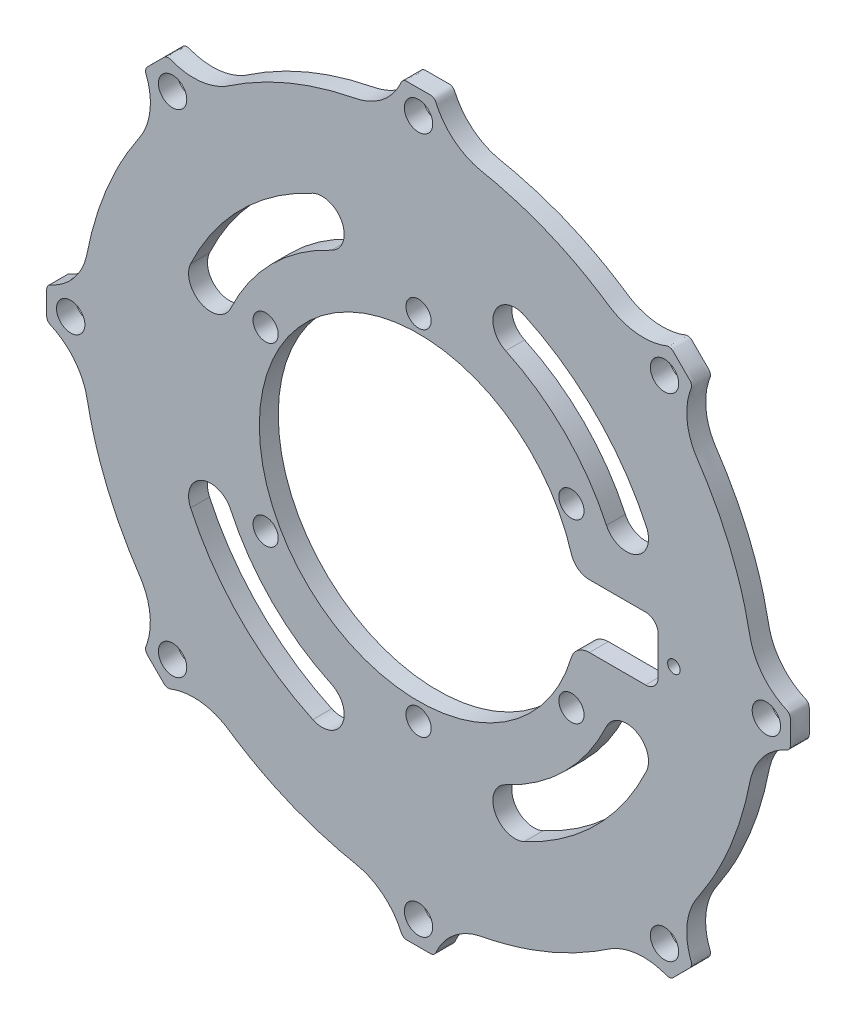
SolidWorks part; units mm, degrees
material "7075-T6, Plate (SS)"
ref_plane "Front Plane" through (0, 0, 0) normal (0, 0, 1) x (1, 0, 0)
ref_plane "Top Plane" through (0, 0, 0) normal (0, 1, 0) x (1, 0, 0)
ref_plane "Right Plane" through (0, 0, 0) normal (1, 0, 0) x (0, 0, -1)
sketch "Sketch1" plane through (0, 0, 0) normal (0, 0, 1) x (1, 0, 0)
  line L0 (0, 0) -> (15.2936, 32.9713) construction
  line L1 (-3.9972, 40.3023) -> (0, 28) construction
  line L3 (38, -3) -> (38, 3) construction
  line L4 (38, -3) -> (38, 3)
  line L5 (36, 5) -> (27.0936, 5)
  line L6 (36, -5) -> (27.0936, -5)
  line L7 (0, 0) -> (0, 48) construction
  line L8 (-2.8886, 58.0903) -> (-2.7624, 58.3675)
  line L9 (-1.8466, 58.9658) -> (1.8466, 58.9658) construction
  line L10 (2.7624, 58.3675) -> (2.7687, 58.3533)
  line L11 (-5, 53.2658) -> (5, 53.2658) construction
  line L12 (40.3894, 43.0009) -> (43.0009, 40.3894) construction
  line L13 (39.3043, 43.2198) -> (39.3187, 43.2254) construction
  line L14 (43.2254, 39.3187) -> (43.2198, 39.3043) construction
  line L15 (58.9658, 1.8466) -> (58.9658, -1.8466) construction
  line L16 (58.3533, 2.7687) -> (58.3675, 2.7624) construction
  line L17 (58.3675, -2.7624) -> (58.3533, -2.7687) construction
  line L18 (43.0009, -40.3894) -> (40.3894, -43.0009) construction
  line L19 (43.2198, -39.3043) -> (43.2254, -39.3187) construction
  line L20 (39.3187, -43.2254) -> (39.3043, -43.2198) construction
  line L21 (1.8466, -58.9658) -> (-1.8466, -58.9658) construction
  line L22 (2.7687, -58.3533) -> (2.7624, -58.3675) construction
  line L23 (-2.7624, -58.3675) -> (-2.7687, -58.3533) construction
  line L24 (-40.3894, -43.0009) -> (-43.0009, -40.3894) construction
  line L25 (-39.3043, -43.2198) -> (-39.3187, -43.2254) construction
  line L26 (-43.2254, -39.3187) -> (-43.2198, -39.3043) construction
  line L27 (-58.9658, -1.8466) -> (-58.9658, 1.8466) construction
  line L28 (-58.3533, -2.7687) -> (-58.3675, -2.7624) construction
  line L29 (-58.3675, 2.7624) -> (-58.3533, 2.7687) construction
  line L30 (-43.0009, 40.3894) -> (-40.3894, 43.0009) construction
  line L31 (-43.2198, 39.3043) -> (-43.2254, 39.3187) construction
  line L32 (-39.3187, 43.2254) -> (-39.3043, 43.2198) construction
  line L33 (0, 0) -> (25.7002, 25.7002) construction
  arc A0 (-10.0483, 52.5479) -> (-30.0517, 44.2622) centre (0, 0) ccw construction
  circle A1 centre (0, 0) radius 28 construction
  arc A3 (24.2164, 7.1504) -> (24.2164, -7.1504) centre (0, 0) ccw
  arc A4 (38, 3) -> (34, 3) centre (36, 3) ccw construction
  arc A5 (34, -3) -> (38, -3) centre (36, -3) ccw construction
  arc A6 (36, -5) -> (38, -3) centre (36, -3) ccw
  arc A7 (38, 3) -> (36, 5) centre (36, 3) ccw
  arc A8 (27.0936, -5) -> (24.2164, -7.1504) centre (27.0936, -8) ccw
  arc A9 (27.0936, 5) -> (24.2164, 7.1504) centre (27.0936, 8) cw
  circle A10 centre (0, 0) radius 36.3456 construction
  arc A13 (15.2936, 32.9713) -> (32.9713, 15.2936) centre (0, 0) cw construction
  circle A72 centre (0, 0) radius 40.5 construction
  circle A81 centre (40.4993, -0.2374) radius 1
  arc A104 (-2.8886, 58.0903) -> (-10.0483, 52.5479) centre (-11.9265, 62.3699) cw construction
  arc A105 (2.7687, 58.3533) -> (10.0483, 52.5479) centre (11.9265, 62.3699) ccw construction
  arc A106 (39.3043, 43.2198) -> (30.0517, 44.2622) centre (35.6689, 52.5355) cw construction
  arc A107 (43.2198, 39.3043) -> (44.2622, 30.0517) centre (52.5355, 35.6689) ccw construction
  arc A108 (58.3533, 2.7687) -> (52.5479, 10.0483) centre (62.3699, 11.9265) cw construction
  arc A109 (58.3533, -2.7687) -> (52.5479, -10.0483) centre (62.3699, -11.9265) ccw construction
  arc A110 (43.2198, -39.3043) -> (44.2622, -30.0517) centre (52.5355, -35.6689) cw construction
  arc A111 (39.3043, -43.2198) -> (30.0517, -44.2622) centre (35.6689, -52.5355) ccw construction
  arc A112 (2.7687, -58.3533) -> (10.0483, -52.5479) centre (11.9265, -62.3699) cw construction
  arc A113 (-2.7687, -58.3533) -> (-10.0483, -52.5479) centre (-11.9265, -62.3699) ccw construction
  arc A114 (-39.3043, -43.2198) -> (-30.0517, -44.2622) centre (-35.6689, -52.5355) cw construction
  arc A115 (-43.2198, -39.3043) -> (-44.2622, -30.0517) centre (-52.5355, -35.6689) ccw construction
  arc A116 (-58.3533, -2.7687) -> (-52.5479, -10.0483) centre (-62.3699, -11.9265) cw construction
  arc A117 (-58.3533, 2.7687) -> (-52.5479, 10.0483) centre (-62.3699, 11.9265) ccw construction
  arc A118 (-43.2198, 39.3043) -> (-44.2622, 30.0517) centre (-52.5355, 35.6689) cw construction
  arc A119 (-39.3043, 43.2198) -> (-30.0517, 44.2622) centre (-35.6689, 52.5355) ccw construction
  arc A120 (30.0517, 44.2622) -> (10.0483, 52.5479) centre (0, 0) ccw construction
  arc A121 (52.5479, 10.0483) -> (44.2622, 30.0517) centre (0, 0) ccw construction
  arc A122 (10.0483, -52.5479) -> (30.0517, -44.2622) centre (0, 0) ccw construction
  arc A123 (44.2622, -30.0517) -> (52.5479, -10.0483) centre (0, 0) ccw construction
  arc A124 (-30.0517, -44.2622) -> (-10.0483, -52.5479) centre (0, 0) ccw construction
  arc A125 (-52.5479, -10.0483) -> (-44.2622, -30.0517) centre (0, 0) ccw construction
  arc A126 (-44.2622, 30.0517) -> (-52.5479, 10.0483) centre (0, 0) ccw construction
  arc A127 (1.8466, 58.9658) -> (2.7624, 58.3675) centre (1.8466, 57.9658) cw construction
  arc A128 (-2.7624, 58.3675) -> (-1.8466, 58.9658) centre (-1.8466, 57.9658) cw construction
  arc A129 (-43.0009, 40.3894) -> (-43.2254, 39.3187) centre (-42.2938, 39.6823) ccw construction
  arc A130 (-40.3894, 43.0009) -> (-39.3187, 43.2254) centre (-39.6823, 42.2938) cw construction
  arc A131 (-58.9658, 1.8466) -> (-58.3675, 2.7624) centre (-57.9658, 1.8466) cw construction
  arc A132 (-58.9658, -1.8466) -> (-58.3675, -2.7624) centre (-57.9658, -1.8466) ccw construction
  arc A133 (-43.0009, -40.3894) -> (-43.2254, -39.3187) centre (-42.2938, -39.6823) cw construction
  arc A134 (-40.3894, -43.0009) -> (-39.3187, -43.2254) centre (-39.6823, -42.2938) ccw construction
  arc A135 (-1.8466, -58.9658) -> (-2.7624, -58.3675) centre (-1.8466, -57.9658) cw construction
  arc A136 (1.8466, -58.9658) -> (2.7624, -58.3675) centre (1.8466, -57.9658) ccw construction
  arc A137 (43.0009, -40.3894) -> (43.2254, -39.3187) centre (42.2938, -39.6823) ccw construction
  arc A138 (40.3894, -43.0009) -> (39.3187, -43.2254) centre (39.6823, -42.2938) cw construction
  arc A139 (58.9658, -1.8466) -> (58.3675, -2.7624) centre (57.9658, -1.8466) cw construction
  arc A140 (58.9658, 1.8466) -> (58.3675, 2.7624) centre (57.9658, 1.8466) ccw construction
  arc A141 (43.0009, 40.3894) -> (43.2254, 39.3187) centre (42.2938, 39.6823) cw construction
  arc A142 (40.3894, 43.0009) -> (39.3187, 43.2254) centre (39.6823, 42.2938) ccw construction
  arc A143 (36.1463, 16.7664) -> (16.7664, 36.1463) centre (0, 0) ccw
  arc A144 (29.7962, 13.8209) -> (13.8209, 29.7962) centre (0, 0) ccw
  arc A145 (29.7962, 13.8209) -> (36.1463, 16.7664) centre (32.9713, 15.2936) ccw
  arc A146 (16.7664, 36.1463) -> (13.8209, 29.7962) centre (15.2936, 32.9713) ccw
  arc A147 (32.9713, -15.2936) -> (15.2936, -32.9713) centre (0, 0) cw construction
  arc A148 (16.7664, -36.1463) -> (36.1463, -16.7664) centre (0, 0) ccw
  arc A149 (13.8209, -29.7962) -> (29.7962, -13.8209) centre (0, 0) ccw
  arc A150 (13.8209, -29.7962) -> (16.7664, -36.1463) centre (15.2936, -32.9713) ccw
  arc A151 (36.1463, -16.7664) -> (29.7962, -13.8209) centre (32.9713, -15.2936) ccw
  arc A152 (-15.2936, -32.9713) -> (-32.9713, -15.2936) centre (0, 0) cw construction
  arc A153 (-36.1463, -16.7664) -> (-16.7664, -36.1463) centre (0, 0) ccw
  arc A154 (-29.7962, -13.8209) -> (-13.8209, -29.7962) centre (0, 0) ccw
  arc A155 (-29.7962, -13.8209) -> (-36.1463, -16.7664) centre (-32.9713, -15.2936) ccw
  arc A156 (-16.7664, -36.1463) -> (-13.8209, -29.7962) centre (-15.2936, -32.9713) ccw
  arc A157 (-32.9713, 15.2936) -> (-15.2936, 32.9713) centre (0, 0) cw construction
  arc A158 (-16.7664, 36.1463) -> (-36.1463, 16.7664) centre (0, 0) ccw
  arc A159 (-13.8209, 29.7962) -> (-29.7962, 13.8209) centre (0, 0) ccw
  arc A160 (-13.8209, 29.7962) -> (-16.7664, 36.1463) centre (-15.2936, 32.9713) ccw
  arc A161 (-36.1463, 16.7664) -> (-29.7962, 13.8209) centre (-32.9713, 15.2936) ccw
  spline S0 degree 3 poles (-2.8886, 58.0903) (-3.9043, 55.9453) (-5.5918, 54.2764) (-7.7481, 53.2847) (-8.2352, 53.0607) (-9.2456, 52.691) (-10.8423, 52.3981) (-11.8892, 52.165) (-12.4107, 52.0406) (-17.936, 50.7229) (-23.1839, 48.5492) (-28.0226, 45.574) (-28.4793, 45.2931) (-29.3844, 44.7177) (-30.7205, 43.7957) (-31.6964, 43.3428) (-32.1993, 43.1567) (-34.5203, 42.2981) (-36.9949, 42.3196) (-39.3007, 43.2183) (-39.3011, 43.2185) (-39.3019, 43.2188) (-39.3031, 43.2193) (-39.3039, 43.2196) (-39.3043, 43.2198) (-39.3047, 43.2199) (-39.3055, 43.2202) (-39.3067, 43.2207) (-39.3075, 43.221) (-39.3079, 43.2212) (-39.3103, 43.2221) (-39.3127, 43.223) (-39.3151, 43.224) (-39.3155, 43.2241) (-39.3163, 43.2245) (-39.3175, 43.2249) (-39.3183, 43.2252) (-39.3187, 43.2254) (-39.3191, 43.2255) (-39.3199, 43.2259) (-39.3211, 43.2263) (-39.3219, 43.2266) (-39.3224, 43.2268) (-39.5998, 43.3338) (-39.8966, 43.3148) (-40.1582, 43.1733) (-40.1864, 43.158) (-40.2413, 43.1248) (-40.3214, 43.0689) (-40.3667, 43.0236) (-40.3894, 43.0009) (-40.412, 42.9783) (-40.4573, 42.933) (-40.5253, 42.865) (-40.5706, 42.8197) (-40.5933, 42.797) (-41.3279, 42.0624) (-42.0624, 41.3279) (-42.797, 40.5933) (-42.8197, 40.5706) (-42.865, 40.5253) (-42.933, 40.4573) (-42.9783, 40.412) (-43.0009, 40.3894) (-43.0236, 40.3667) (-43.0689, 40.3214) (-43.1248, 40.2413) (-43.158, 40.1864) (-43.1733, 40.1582) (-43.3148, 39.8966) (-43.3338, 39.5998) (-43.2268, 39.3224) (-43.2266, 39.3219) (-43.2263, 39.3211) (-43.2259, 39.3199) (-43.2255, 39.3191) (-43.2254, 39.3187) (-43.2252, 39.3183) (-43.2249, 39.3175) (-43.2245, 39.3163) (-43.2241, 39.3155) (-43.224, 39.3151) (-43.223, 39.3127) (-43.2221, 39.3103) (-43.2212, 39.3079) (-43.221, 39.3075) (-43.2207, 39.3067) (-43.2202, 39.3055) (-43.2199, 39.3047) (-43.2198, 39.3043) (-43.2196, 39.3039) (-43.2193, 39.3031) (-43.2188, 39.3019) (-43.2185, 39.3011) (-43.2183, 39.3007) (-42.3196, 36.9949) (-42.2981, 34.5203) (-43.1567, 32.1993) (-43.3428, 31.6964) (-43.7957, 30.7205) (-44.7177, 29.3844) (-45.2931, 28.4793) (-45.574, 28.0226) (-48.5492, 23.1839) (-50.7229, 17.936) (-52.0406, 12.4107) (-52.165, 11.8892) (-52.3981, 10.8423) (-52.691, 9.2456) (-53.0607, 8.2352) (-53.2847, 7.7481) (-54.3188, 5.4997) (-56.0838, 3.7651) (-58.3498, 2.7702) (-58.3502, 2.77) (-58.3509, 2.7697) (-58.3521, 2.7692) (-58.3529, 2.7688) (-58.3533, 2.7687) (-58.3537, 2.7685) (-58.3545, 2.7681) (-58.3557, 2.7676) (-58.3565, 2.7673) (-58.3569, 2.7671) (-58.3592, 2.7661) (-58.3616, 2.765) (-58.364, 2.764) (-58.3644, 2.7638) (-58.3651, 2.7635) (-58.3663, 2.7629) (-58.3671, 2.7626) (-58.3675, 2.7624) (-58.3679, 2.7623) (-58.3687, 2.7619) (-58.3699, 2.7614) (-58.3707, 2.761) (-58.3711, 2.7609) (-58.643, 2.6403) (-58.8394, 2.417) (-58.9243, 2.132) (-58.9334, 2.1013) (-58.9487, 2.039) (-58.9658, 1.9428) (-58.9658, 1.8787) (-58.9658, 1.8466) (-58.9658, 1.8146) (-58.9658, 1.7505) (-58.9658, 1.6544) (-58.9658, 1.5903) (-58.9658, 1.5583) (-58.9658, 0.5194) (-58.9658, -0.5194) (-58.9658, -1.5583) (-58.9658, -1.5903) (-58.9658, -1.6544) (-58.9658, -1.7505) (-58.9658, -1.8146) (-58.9658, -1.8466) (-58.9658, -1.8787) (-58.9658, -1.9428) (-58.9487, -2.039) (-58.9334, -2.1013) (-58.9243, -2.132) (-58.8394, -2.417) (-58.643, -2.6403) (-58.3711, -2.7609) (-58.3707, -2.761) (-58.3699, -2.7614) (-58.3687, -2.7619) (-58.3679, -2.7623) (-58.3675, -2.7624) (-58.3671, -2.7626) (-58.3663, -2.7629) (-58.3651, -2.7635) (-58.3644, -2.7638) (-58.364, -2.764) (-58.3616, -2.765) (-58.3592, -2.7661) (-58.3569, -2.7671) (-58.3565, -2.7673) (-58.3557, -2.7676) (-58.3545, -2.7681) (-58.3537, -2.7685) (-58.3533, -2.7687) (-58.3529, -2.7688) (-58.3521, -2.7692) (-58.3509, -2.7697) (-58.3502, -2.77) (-58.3498, -2.7702) (-56.0838, -3.7651) (-54.3188, -5.4997) (-53.2847, -7.7481) (-53.0607, -8.2352) (-52.691, -9.2456) (-52.3981, -10.8423) (-52.165, -11.8892) (-52.0406, -12.4107) (-50.7229, -17.936) (-48.5492, -23.1839) (-45.574, -28.0226) (-45.2931, -28.4793) (-44.7177, -29.3844) (-43.7957, -30.7205) (-43.3428, -31.6964) (-43.1567, -32.1993) (-42.2981, -34.5203) (-42.3196, -36.9949) (-43.2183, -39.3007) (-43.2185, -39.3011) (-43.2188, -39.3019) (-43.2193, -39.3031) (-43.2196, -39.3039) (-43.2198, -39.3043) (-43.2199, -39.3047) (-43.2202, -39.3055) (-43.2207, -39.3067) (-43.221, -39.3075) (-43.2212, -39.3079) (-43.2221, -39.3103) (-43.223, -39.3127) (-43.224, -39.3151) (-43.2241, -39.3155) (-43.2245, -39.3163) (-43.2249, -39.3175) (-43.2252, -39.3183) (-43.2254, -39.3187) (-43.2255, -39.3191) (-43.2259, -39.3199) (-43.2263, -39.3211) (-43.2266, -39.3219) (-43.2268, -39.3224) (-43.3338, -39.5998) (-43.3148, -39.8966) (-43.1733, -40.1582) (-43.158, -40.1864) (-43.1248, -40.2413) (-43.0689, -40.3214) (-43.0236, -40.3667) (-43.0009, -40.3894) (-42.9783, -40.412) (-42.933, -40.4573) (-42.865, -40.5253) (-42.8197, -40.5706) (-42.797, -40.5933) (-42.0624, -41.3279) (-41.3279, -42.0624) (-40.5933, -42.797) (-40.5706, -42.8197) (-40.5253, -42.865) (-40.4573, -42.933) (-40.412, -42.9783) (-40.3894, -43.0009) (-40.3667, -43.0236) (-40.3214, -43.0689) (-40.2413, -43.1248) (-40.1864, -43.158) (-40.1582, -43.1733) (-39.8966, -43.3148) (-39.5998, -43.3338) (-39.3224, -43.2268) (-39.3219, -43.2266) (-39.3211, -43.2263) (-39.3199, -43.2259) (-39.3191, -43.2255) (-39.3187, -43.2254) (-39.3183, -43.2252) (-39.3175, -43.2249) (-39.3163, -43.2245) (-39.3155, -43.2241) (-39.3151, -43.224) (-39.3127, -43.223) (-39.3103, -43.2221) (-39.3079, -43.2212) (-39.3075, -43.221) (-39.3067, -43.2207) (-39.3055, -43.2202) (-39.3047, -43.2199) (-39.3043, -43.2198) (-39.3039, -43.2196) (-39.3031, -43.2193) (-39.3019, -43.2188) (-39.3011, -43.2185) (-39.3007, -43.2183) (-36.9949, -42.3196) (-34.5203, -42.2981) (-32.1993, -43.1567) (-31.6964, -43.3428) (-30.7205, -43.7957) (-29.3844, -44.7177) (-28.4793, -45.2931) (-28.0226, -45.574) (-23.1839, -48.5492) (-17.936, -50.7229) (-12.4107, -52.0406) (-11.8892, -52.165) (-10.8423, -52.3981) (-9.2456, -52.691) (-8.2352, -53.0607) (-7.7481, -53.2847) (-5.4997, -54.3188) (-3.7651, -56.0838) (-2.7702, -58.3498) (-2.77, -58.3502) (-2.7697, -58.3509) (-2.7692, -58.3521) (-2.7688, -58.3529) (-2.7687, -58.3533) (-2.7685, -58.3537) (-2.7681, -58.3545) (-2.7676, -58.3557) (-2.7673, -58.3565) (-2.7671, -58.3569) (-2.7661, -58.3592) (-2.765, -58.3616) (-2.764, -58.364) (-2.7638, -58.3644) (-2.7635, -58.3651) (-2.7629, -58.3663) (-2.7626, -58.3671) (-2.7624, -58.3675) (-2.7623, -58.3679) (-2.7619, -58.3687) (-2.7614, -58.3699) (-2.761, -58.3707) (-2.7609, -58.3711) (-2.6403, -58.643) (-2.417, -58.8394) (-2.132, -58.9243) (-2.1013, -58.9334) (-2.039, -58.9487) (-1.9428, -58.9658) (-1.8787, -58.9658) (-1.8466, -58.9658) (-1.8146, -58.9658) (-1.7505, -58.9658) (-1.6544, -58.9658) (-1.5903, -58.9658) (-1.5583, -58.9658) (-0.5194, -58.9658) (0.5194, -58.9658) (1.5583, -58.9658) (1.5903, -58.9658) (1.6544, -58.9658) (1.7505, -58.9658) (1.8146, -58.9658) (1.8466, -58.9658) (1.8787, -58.9658) (1.9428, -58.9658) (2.039, -58.9487) (2.1013, -58.9334) (2.132, -58.9243) (2.417, -58.8394) (2.6403, -58.643) (2.7609, -58.3711) (2.761, -58.3707) (2.7614, -58.3699) (2.7619, -58.3687) (2.7623, -58.3679) (2.7624, -58.3675) (2.7626, -58.3671) (2.7629, -58.3663) (2.7635, -58.3651) (2.7638, -58.3644) (2.764, -58.364) (2.765, -58.3616) (2.7661, -58.3592) (2.7671, -58.3569) (2.7673, -58.3565) (2.7676, -58.3557) (2.7681, -58.3545) (2.7685, -58.3537) (2.7687, -58.3533) (2.7688, -58.3529) (2.7692, -58.3521) (2.7697, -58.3509) (2.77, -58.3502) (2.7702, -58.3498) (3.7651, -56.0838) (5.4997, -54.3188) (7.7481, -53.2847) (8.2352, -53.0607) (9.2456, -52.691) (10.8423, -52.3981) (11.8892, -52.165) (12.4107, -52.0406) (17.936, -50.7229) (23.1839, -48.5492) (28.0226, -45.574) (28.4793, -45.2931) (29.3844, -44.7177) (30.7205, -43.7957) (31.6964, -43.3428) (32.1993, -43.1567) (34.5203, -42.2981) (36.9949, -42.3196) (39.3007, -43.2183) (39.3011, -43.2185) (39.3019, -43.2188) (39.3031, -43.2193) (39.3039, -43.2196) (39.3043, -43.2198) (39.3047, -43.2199) (39.3055, -43.2202) (39.3067, -43.2207) (39.3075, -43.221) (39.3079, -43.2212) (39.3103, -43.2221) (39.3127, -43.223) (39.3151, -43.224) (39.3155, -43.2241) (39.3163, -43.2245) (39.3175, -43.2249) (39.3183, -43.2252) (39.3187, -43.2254) (39.3191, -43.2255) (39.3199, -43.2259) (39.3211, -43.2263) (39.3219, -43.2266) (39.3224, -43.2268) (39.5998, -43.3338) (39.8966, -43.3148) (40.1582, -43.1733) (40.1864, -43.158) (40.2413, -43.1248) (40.3214, -43.0689) (40.3667, -43.0236) (40.3894, -43.0009) (40.412, -42.9783) (40.4573, -42.933) (40.5253, -42.865) (40.5706, -42.8197) (40.5933, -42.797) (41.3279, -42.0624) (42.0624, -41.3279) (42.797, -40.5933) (42.8197, -40.5706) (42.865, -40.5253) (42.933, -40.4573) (42.9783, -40.412) (43.0009, -40.3894) (43.0236, -40.3667) (43.0689, -40.3214) (43.1248, -40.2413) (43.158, -40.1864) (43.1733, -40.1582) (43.3148, -39.8966) (43.3338, -39.5998) (43.2268, -39.3224) (43.2266, -39.3219) (43.2263, -39.3211) (43.2259, -39.3199) (43.2255, -39.3191) (43.2254, -39.3187) (43.2252, -39.3183) (43.2249, -39.3175) (43.2245, -39.3163) (43.2241, -39.3155) (43.224, -39.3151) (43.223, -39.3127) (43.2221, -39.3103) (43.2212, -39.3079) (43.221, -39.3075) (43.2207, -39.3067) (43.2202, -39.3055) (43.2199, -39.3047) (43.2198, -39.3043) (43.2196, -39.3039) (43.2193, -39.3031) (43.2188, -39.3019) (43.2185, -39.3011) (43.2183, -39.3007) (42.3196, -36.9949) (42.2981, -34.5203) (43.1567, -32.1993) (43.3428, -31.6964) (43.7957, -30.7205) (44.7177, -29.3844) (45.2931, -28.4793) (45.574, -28.0226) (48.5492, -23.1839) (50.7229, -17.936) (52.0406, -12.4107) (52.165, -11.8892) (52.3981, -10.8423) (52.691, -9.2456) (53.0607, -8.2352) (53.2847, -7.7481) (54.3188, -5.4997) (56.0838, -3.7651) (58.3498, -2.7702) (58.3502, -2.77) (58.3509, -2.7697) (58.3521, -2.7692) (58.3529, -2.7688) (58.3533, -2.7687) (58.3537, -2.7685) (58.3545, -2.7681) (58.3557, -2.7676) (58.3565, -2.7673) (58.3569, -2.7671) (58.3592, -2.7661) (58.3616, -2.765) (58.364, -2.764) (58.3644, -2.7638) (58.3651, -2.7635) (58.3663, -2.7629) (58.3671, -2.7626) (58.3675, -2.7624) (58.3679, -2.7623) (58.3687, -2.7619) (58.3699, -2.7614) (58.3707, -2.761) (58.3711, -2.7609) (58.643, -2.6403) (58.8394, -2.417) (58.9243, -2.132) (58.9334, -2.1013) (58.9487, -2.039) (58.9658, -1.9428) (58.9658, -1.8787) (58.9658, -1.8466) (58.9658, -1.8146) (58.9658, -1.7505) (58.9658, -1.6544) (58.9658, -1.5903) (58.9658, -1.5583) (58.9658, -0.5194) (58.9658, 0.5194) (58.9658, 1.5583) (58.9658, 1.5903) (58.9658, 1.6544) (58.9658, 1.7505) (58.9658, 1.8146) (58.9658, 1.8466) (58.9658, 1.8787) (58.9658, 1.9428) (58.9487, 2.039) (58.9334, 2.1013) (58.9243, 2.132) (58.8394, 2.417) (58.643, 2.6403) (58.3711, 2.7609) (58.3707, 2.761) (58.3699, 2.7614) (58.3687, 2.7619) (58.3679, 2.7623) (58.3675, 2.7624) (58.3671, 2.7626) (58.3663, 2.7629) (58.3651, 2.7635) (58.3644, 2.7638) (58.364, 2.764) (58.3616, 2.765) (58.3592, 2.7661) (58.3569, 2.7671) (58.3565, 2.7673) (58.3557, 2.7676) (58.3545, 2.7681) (58.3537, 2.7685) (58.3533, 2.7687) (58.3529, 2.7688) (58.3521, 2.7692) (58.3509, 2.7697) (58.3502, 2.77) (58.3498, 2.7702) (56.0838, 3.7651) (54.3188, 5.4997) (53.2847, 7.7481) (53.0607, 8.2352) (52.691, 9.2456) (52.3981, 10.8423) (52.165, 11.8892) (52.0406, 12.4107) (50.7229, 17.936) (48.5492, 23.1839) (45.574, 28.0226) (45.2931, 28.4793) (44.7177, 29.3844) (43.7957, 30.7205) (43.3428, 31.6964) (43.1567, 32.1993) (42.2981, 34.5203) (42.3196, 36.9949) (43.2183, 39.3007) (43.2185, 39.3011) (43.2188, 39.3019) (43.2193, 39.3031) (43.2196, 39.3039) (43.2198, 39.3043) (43.2199, 39.3047) (43.2202, 39.3055) (43.2207, 39.3067) (43.221, 39.3075) (43.2212, 39.3079) (43.2221, 39.3103) (43.223, 39.3127) (43.224, 39.3151) (43.2241, 39.3155) (43.2245, 39.3163) (43.2249, 39.3175) (43.2252, 39.3183) (43.2254, 39.3187) (43.2255, 39.3191) (43.2259, 39.3199) (43.2263, 39.3211) (43.2266, 39.3219) (43.2268, 39.3224) (43.3338, 39.5998) (43.3148, 39.8966) (43.1733, 40.1582) (43.158, 40.1864) (43.1248, 40.2413) (43.0689, 40.3214) (43.0236, 40.3667) (43.0009, 40.3894) (42.9783, 40.412) (42.933, 40.4573) (42.865, 40.5253) (42.8197, 40.5706) (42.797, 40.5933) (42.0624, 41.3279) (41.3279, 42.0624) (40.5933, 42.797) (40.5706, 42.8197) (40.5253, 42.865) (40.4573, 42.933) (40.412, 42.9783) (40.3894, 43.0009) (40.3667, 43.0236) (40.3214, 43.0689) (40.2413, 43.1248) (40.1864, 43.158) (40.1582, 43.1733) (39.8966, 43.3148) (39.5998, 43.3338) (39.3224, 43.2268) (39.3219, 43.2266) (39.3211, 43.2263) (39.3199, 43.2259) (39.3191, 43.2255) (39.3187, 43.2254) (39.3183, 43.2252) (39.3175, 43.2249) (39.3163, 43.2245) (39.3155, 43.2241) (39.3151, 43.224) (39.3127, 43.223) (39.3103, 43.2221) (39.3079, 43.2212) (39.3075, 43.221) (39.3067, 43.2207) (39.3055, 43.2202) (39.3047, 43.2199) (39.3043, 43.2198) (39.3039, 43.2196) (39.3031, 43.2193) (39.3019, 43.2188) (39.3011, 43.2185) (39.3007, 43.2183) (36.9949, 42.3196) (34.5203, 42.2981) (32.1993, 43.1567) (31.6964, 43.3428) (30.7205, 43.7957) (29.3844, 44.7177) (28.4793, 45.2931) (28.0226, 45.574) (23.1839, 48.5492) (17.936, 50.7229) (12.4107, 52.0406) (11.8892, 52.165) (10.8423, 52.3981) (9.2456, 52.691) (8.2352, 53.0607) (7.7481, 53.2847) (5.5918, 54.2764) (3.9043, 55.9453) (2.8886, 58.0903) (2.8604, 58.1497) (2.8053, 58.2691) (2.7273, 58.4532) (2.6522, 58.562) (2.6097, 58.6121) (2.4833, 58.7614) (2.3195, 58.8684) (2.132, 58.9243) (2.1013, 58.9334) (2.039, 58.9487) (1.9428, 58.9658) (1.8787, 58.9658) (1.8466, 58.9658) (1.8146, 58.9658) (1.7505, 58.9658) (1.6544, 58.9658) (1.5903, 58.9658) (1.5583, 58.9658) (0.5194, 58.9658) (-0.5194, 58.9658) (-1.5583, 58.9658) (-1.5903, 58.9658) (-1.6544, 58.9658) (-1.7505, 58.9658) (-1.8146, 58.9658) (-1.8466, 58.9658) (-1.8787, 58.9658) (-1.9428, 58.9658) (-2.039, 58.9487) (-2.1013, 58.9334) (-2.132, 58.9243) (-2.3195, 58.8684) (-2.4833, 58.7614) (-2.6097, 58.6121) (-2.6522, 58.562) (-2.7273, 58.4532) (-2.8053, 58.2691) (-2.8604, 58.1497) (-2.8886, 58.0903) (-3.9043, 55.9453) (-5.5918, 54.2764) knots -0.000527 0 0 0 0.018272 0.018272 0.018272 0.022573 0.026874 0.031175 0.031175 0.031175 0.076354 0.076354 0.076354 0.080654 0.084955 0.089256 0.089256 0.089256 0.108243 0.108243 0.108243 0.108247 0.10825 0.108253 0.108253 0.108253 0.108257 0.10826 0.108264 0.108264 0.108264 0.108285 0.108285 0.108285 0.108288 0.108291 0.108295 0.108295 0.108295 0.108298 0.108302 0.108305 0.108305 0.108305 0.110545 0.110545 0.110545 0.110802 0.111059 0.111316 0.111316 0.111316 0.111573 0.11183 0.112087 0.112087 0.112087 0.120419 0.120419 0.120419 0.120676 0.120933 0.12119 0.12119 0.12119 0.121447 0.121704 0.121961 0.121961 0.121961 0.1242 0.1242 0.1242 0.124204 0.124207 0.124211 0.124211 0.124211 0.124214 0.124218 0.124221 0.124221 0.124221 0.124242 0.124242 0.124242 0.124245 0.124249 0.124252 0.124252 0.124252 0.124256 0.124259 0.124262 0.124262 0.124262 0.14325 0.14325 0.14325 0.14755 0.151851 0.156152 0.156152 0.156152 0.201331 0.201331 0.201331 0.205632 0.209932 0.214233 0.214233 0.214233 0.23322 0.23322 0.23322 0.233224 0.233227 0.233231 0.233231 0.233231 0.233234 0.233237 0.233241 0.233241 0.233241 0.233262 0.233262 0.233262 0.233265 0.233269 0.233272 0.233272 0.233272 0.233275 0.233279 0.233282 0.233282 0.233282 0.235522 0.235522 0.235522 0.235779 0.236036 0.236293 0.236293 0.236293 0.23655 0.236807 0.237064 0.237064 0.237064 0.245396 0.245396 0.245396 0.245653 0.24591 0.246167 0.246167 0.246167 0.246424 0.246681 0.246938 0.246938 0.246938 0.249177 0.249177 0.249177 0.249181 0.249184 0.249188 0.249188 0.249188 0.249191 0.249195 0.249198 0.249198 0.249198 0.249219 0.249219 0.249219 0.249222 0.249226 0.249229 0.249229 0.249229 0.249233 0.249236 0.24924 0.24924 0.24924 0.268227 0.268227 0.268227 0.272527 0.276828 0.281129 0.281129 0.281129 0.326308 0.326308 0.326308 0.330609 0.33491 0.33921 0.33921 0.33921 0.358197 0.358197 0.358197 0.358201 0.358204 0.358208 0.358208 0.358208 0.358211 0.358215 0.358218 0.358218 0.358218 0.358239 0.358239 0.358239 0.358242 0.358246 0.358249 0.358249 0.358249 0.358253 0.358256 0.35826 0.35826 0.35826 0.360499 0.360499 0.360499 0.360756 0.361013 0.36127 0.36127 0.36127 0.361527 0.361784 0.362041 0.362041 0.362041 0.370373 0.370373 0.370373 0.37063 0.370887 0.371144 0.371144 0.371144 0.371401 0.371658 0.371915 0.371915 0.371915 0.374155 0.374155 0.374155 0.374158 0.374161 0.374165 0.374165 0.374165 0.374168 0.374172 0.374175 0.374175 0.374175 0.374196 0.374196 0.374196 0.374199 0.374203 0.374206 0.374206 0.374206 0.37421 0.374213 0.374217 0.374217 0.374217 0.393204 0.393204 0.393204 0.397505 0.401805 0.406106 0.406106 0.406106 0.451285 0.451285 0.451285 0.455586 0.459887 0.464187 0.464187 0.464187 0.483175 0.483175 0.483175 0.483178 0.483181 0.483185 0.483185 0.483185 0.483188 0.483192 0.483195 0.483195 0.483195 0.483216 0.483216 0.483216 0.483219 0.483223 0.483226 0.483226 0.483226 0.48323 0.483233 0.483237 0.483237 0.483237 0.485476 0.485476 0.485476 0.485733 0.48599 0.486247 0.486247 0.486247 0.486504 0.486761 0.487018 0.487018 0.487018 0.49535 0.49535 0.49535 0.495607 0.495864 0.496121 0.496121 0.496121 0.496378 0.496635 0.496892 0.496892 0.496892 0.499132 0.499132 0.499132 0.499135 0.499139 0.499142 0.499142 0.499142 0.499146 0.499149 0.499152 0.499152 0.499152 0.499173 0.499173 0.499173 0.499177 0.49918 0.499184 0.499184 0.499184 0.499187 0.49919 0.499194 0.499194 0.499194 0.518181 0.518181 0.518181 0.522482 0.526783 0.531083 0.531083 0.531083 0.576262 0.576262 0.576262 0.580563 0.584864 0.589165 0.589165 0.589165 0.608152 0.608152 0.608152 0.608155 0.608159 0.608162 0.608162 0.608162 0.608166 0.608169 0.608172 0.608172 0.608172 0.608193 0.608193 0.608193 0.608197 0.6082 0.608203 0.608203 0.608203 0.608207 0.60821 0.608214 0.608214 0.608214 0.610453 0.610453 0.610453 0.61071 0.610967 0.611224 0.611224 0.611224 0.611481 0.611738 0.611995 0.611995 0.611995 0.620328 0.620328 0.620328 0.620585 0.620842 0.621099 0.621099 0.621099 0.621356 0.621613 0.62187 0.62187 0.62187 0.624109 0.624109 0.624109 0.624112 0.624116 0.624119 0.624119 0.624119 0.624123 0.624126 0.62413 0.62413 0.62413 0.62415 0.62415 0.62415 0.624154 0.624157 0.624161 0.624161 0.624161 0.624164 0.624168 0.624171 0.624171 0.624171 0.643158 0.643158 0.643158 0.647459 0.65176 0.65606 0.65606 0.65606 0.701239 0.701239 0.701239 0.70554 0.709841 0.714142 0.714142 0.714142 0.733129 0.733129 0.733129 0.733132 0.733136 0.733139 0.733139 0.733139 0.733143 0.733146 0.73315 0.73315 0.73315 0.73317 0.73317 0.73317 0.733174 0.733177 0.733181 0.733181 0.733181 0.733184 0.733188 0.733191 0.733191 0.733191 0.73543 0.73543 0.73543 0.735687 0.735944 0.736201 0.736201 0.736201 0.736458 0.736715 0.736972 0.736972 0.736972 0.745305 0.745305 0.745305 0.745562 0.745819 0.746076 0.746076 0.746076 0.746333 0.74659 0.746847 0.746847 0.746847 0.749086 0.749086 0.749086 0.749089 0.749093 0.749096 0.749096 0.749096 0.7491 0.749103 0.749107 0.749107 0.749107 0.749127 0.749127 0.749127 0.749131 0.749134 0.749138 0.749138 0.749138 0.749141 0.749145 0.749148 0.749148 0.749148 0.768135 0.768135 0.768135 0.772436 0.776737 0.781038 0.781038 0.781038 0.826217 0.826217 0.826217 0.830517 0.834818 0.839119 0.839119 0.839119 0.858106 0.858106 0.858106 0.858109 0.858113 0.858116 0.858116 0.858116 0.85812 0.858123 0.858127 0.858127 0.858127 0.858147 0.858147 0.858147 0.858151 0.858154 0.858158 0.858158 0.858158 0.858161 0.858165 0.858168 0.858168 0.858168 0.860408 0.860408 0.860408 0.860665 0.860921 0.861178 0.861178 0.861178 0.861435 0.861692 0.861949 0.861949 0.861949 0.870282 0.870282 0.870282 0.870539 0.870796 0.871053 0.871053 0.871053 0.87131 0.871567 0.871824 0.871824 0.871824 0.874063 0.874063 0.874063 0.874067 0.87407 0.874074 0.874074 0.874074 0.874077 0.87408 0.874084 0.874084 0.874084 0.874105 0.874105 0.874105 0.874108 0.874112 0.874115 0.874115 0.874115 0.874118 0.874122 0.874125 0.874125 0.874125 0.893112 0.893112 0.893112 0.897413 0.901714 0.906015 0.906015 0.906015 0.951194 0.951194 0.951194 0.955495 0.959795 0.964096 0.964096 0.964096 0.982368 0.982368 0.982368 0.982896 0.983423 0.98395 0.98395 0.98395 0.985476 0.985476 0.985476 0.985733 0.98599 0.986247 0.986247 0.986247 0.986504 0.986761 0.987018 0.987018 0.987018 0.99535 0.99535 0.99535 0.995607 0.995864 0.996121 0.996121 0.996121 0.996378 0.996635 0.996892 0.996892 0.996892 0.998418 0.998418 0.998418 0.998945 0.999473 1 1 1 1.018272 1.018272 1.018272 weights 1 0.959869 0.959869 1 1 1 1 1 1 0.991634 0.991634 1 1 1 1 1 1 0.956557 0.956557 1 1 1 1 1 1 1 1 1 1 1 1 1 1 1 1 1 1 1 1 1 1 1 1 0.938724 0.938724 1 1 1 1 1 1 1 1 1 1 1 1 1 1 1 1 1 1 1 1 1 1 1 1 0.938724 0.938724 1 1 1 1 1 1 1 1 1 1 1 1 1 1 1 1 1 1 1 1 1 1 1 1 0.956557 0.956557 1 1 1 1 1 1 0.991634 0.991634 1 1 1 1 1 1 0.956557 0.956557 1 1 1 1 1 1 1 1 1 1 1 1 1 1 1 1 1 1 1 1 1 1 1 1 0.938724 0.938724 1 1 1 1 1 1 1 1 1 1 1 1 1 1 1 1 1 1 1 1 1 1 1 1 0.938724 0.938724 1 1 1 1 1 1 1 1 1 1 1 1 1 1 1 1 1 1 1 1 1 1 1 1 0.956557 0.956557 1 1 1 1 1 1 0.991634 0.991634 1 1 1 1 1 1 0.956557 0.956557 1 1 1 1 1 1 1 1 1 1 1 1 1 1 1 1 1 1 1 1 1 1 1 1 0.938724 0.938724 1 1 1 1 1 1 1 1 1 1 1 1 1 1 1 1 1 1 1 1 1 1 1 1 0.938724 0.938724 1 1 1 1 1 1 1 1 1 1 1 1 1 1 1 1 1 1 1 1 1 1 1 1 0.956557 0.956557 1 1 1 1 1 1 0.991634 0.991634 1 1 1 1 1 1 0.956557 0.956557 1 1 1 1 1 1 1 1 1 1 1 1 1 1 1 1 1 1 1 1 1 1 1 1 0.938724 0.938724 1 1 1 1 1 1 1 1 1 1 1 1 1 1 1 1 1 1 1 1 1 1 1 1 0.938724 0.938724 1 1 1 1 1 1 1 1 1 1 1 1 1 1 1 1 1 1 1 1 1 1 1 1 0.956557 0.956557 1 1 1 1 1 1 0.991634 0.991634 1 1 1 1 1 1 0.956557 0.956557 1 1 1 1 1 1 1 1 1 1 1 1 1 1 1 1 1 1 1 1 1 1 1 1 0.938724 0.938724 1 1 1 1 1 1 1 1 1 1 1 1 1 1 1 1 1 1 1 1 1 1 1 1 0.938724 0.938724 1 1 1 1 1 1 1 1 1 1 1 1 1 1 1 1 1 1 1 1 1 1 1 1 0.956557 0.956557 1 1 1 1 1 1 0.991634 0.991634 1 1 1 1 1 1 0.956557 0.956557 1 1 1 1 1 1 1 1 1 1 1 1 1 1 1 1 1 1 1 1 1 1 1 1 0.938724 0.938724 1 1 1 1 1 1 1 1 1 1 1 1 1 1 1 1 1 1 1 1 1 1 1 1 0.938724 0.938724 1 1 1 1 1 1 1 1 1 1 1 1 1 1 1 1 1 1 1 1 1 1 1 1 0.956557 0.956557 1 1 1 1 1 1 0.991634 0.991634 1 1 1 1 1 1 0.956557 0.956557 1 1 1 1 1 1 1 1 1 1 1 1 1 1 1 1 1 1 1 1 1 1 1 1 0.938724 0.938724 1 1 1 1 1 1 1 1 1 1 1 1 1 1 1 1 1 1 1 1 1 1 1 1 0.938724 0.938724 1 1 1 1 1 1 1 1 1 1 1 1 1 1 1 1 1 1 1 1 1 1 1 1 0.956557 0.956557 1 1 1 1 1 1 0.991634 0.991634 1 1 1 1 1 1 0.959869 0.959869 1 1 1 1 1 1 0.972283 0.972283 1 1 1 1 1 1 1 1 1 1 1 1 1 1 1 1 1 1 1 1 1 1 1 1 0.972283 0.972283 1 1 1 1 1 1 0.959869 0.959869 only from (-2.8886, 58.0903) to (-2.8886, 58.0903)
  point P4 (0, 28)
  point P5 (24.2487, 14)
  point P9 (24.2487, -14)
  point P10 (0, -28)
  point P11 (-24.2487, -14)
  point P12 (-24.2487, 14)
  point P13 (0, 0)
  point P29 (25.7002, 25.7002)
  point P44 (25.7002, -25.7002)
  point P51 (-25.7002, -25.7002)
  point P58 (-25.7002, 25.7002)
  point P63 (0, 0)
  point P154 (0, 0)
  point P157 (0, 48)
  point P216 (0, 0)
  point P228 (2.5, 58.9658)
  point P285 (0, 0)
  point P288 (-2.5, 58.9658)
  point P317 (39.0081, 39.0081)
  point P318 (0, 55.1658)
  point P319 (0, 24)
  point P320 (55.1658, 0)
  point P323 (39.0081, -39.0081)
  point P324 (0, -55.1658)
  point P325 (-39.0081, -39.0081)
  point P326 (-55.1658, 0)
  point P327 (-39.0081, 39.0081)
  point P328 (0, 0)
  dimension "D1" = 56
  dimension "D2" = 107
  dimension "D3" = 6
  dimension "D4" = 50.5
  dimension "D5" = 3
  dimension "D6" = 2
  dimension "D7" = 40.4993
  dimension "D8" = 0.2374
  dimension "D9" = 18
  dimension "81" = 81
  dimension "D10" = 3.5
  dimension "D13" = 5.7
  dimension "D16" = 10
  dimension "D19" = 1
  dimension "D20" = 1
  dimension "D12" = 48
  dimension "D14" = 5
  dimension "D15" = 10
  dimension "D18" = 3.8
  dimension "D21" = 8
  dimension "D11" = 25
  dimension "D22" = 45
  dimension "D17" = 8
  dimension "D23" = 4
extrude "Boss-Extrude1" add sketch "Sketch1" along normal blind 3 contours A0 A81 region at (-1.3175, 57.5136, 0)
hole_wizard "Ø4.0mm Dowel Hole1" positions "Sketch4" profile "Sketch5" hole size "Ø4.0" standard "ISO"
sketch "Sketch4" plane through (0, 0, 3) normal (0, 0, 1) x (1, 0, 0)
  point P0 (0, 28)
  point P3 (24.2487, 14)
  point P6 (24.2487, -14)
  point P9 (0, -28)
  point P12 (-24.2487, -14)
  point P15 (-24.2487, 14)
sketch "Sketch5" plane through (0, 28, 3) normal (1, 0, 0) x (0, -1, 0)
  line L0 (0, 0) -> (0, 5.2017)
  line L1 (0, 5.2017) -> (2, 4)
  line L2 (2, 4) -> (2, 0)
  line L5 (2, 0) -> (0, 0)
  line L10 (0, 5.2017) -> (-2, 4) construction
  line L11 (0, -6.35) -> (0, 107.95) construction
  dimension "Hole Dia." = 4
  dimension "Hole Depth" = 4
  dimension "Drill Angle" = 118
hole_wizard "M4 Clearance Hole1" positions "Sketch14" profile "Sketch15" hole size "M4" standard "ISO"
sketch "Sketch14" plane through (0, 0, 3) normal (0, 0, 1) x (1, 0, 0)
  point P0 (0, 55.1658)
  point P3 (-39.0081, 39.0081)
  point P6 (39.0081, 39.0081)
  point P9 (55.1658, 0)
  point P12 (39.0081, -39.0081)
  point P15 (-55.1658, 0)
  point P18 (-39.0081, -39.0081)
  point P21 (0, -55.1658)
sketch "Sketch15" plane through (0, 55.1658, 3) normal (1, 0, 0) x (0, -1, 0)
  line L0 (0, 0) -> (0, 5.3519)
  line L1 (0, 5.3519) -> (2.25, 4)
  line L2 (2.25, 4) -> (2.25, 0)
  line L5 (2.25, 0) -> (0, 0)
  line L10 (0, 5.3519) -> (-2.25, 4) construction
  line L11 (0, -6.35) -> (0, 107.95) construction
  dimension "Hole Dia." = 4.5
  dimension "Hole Depth" = 4
  dimension "Drill Angle" = 118
